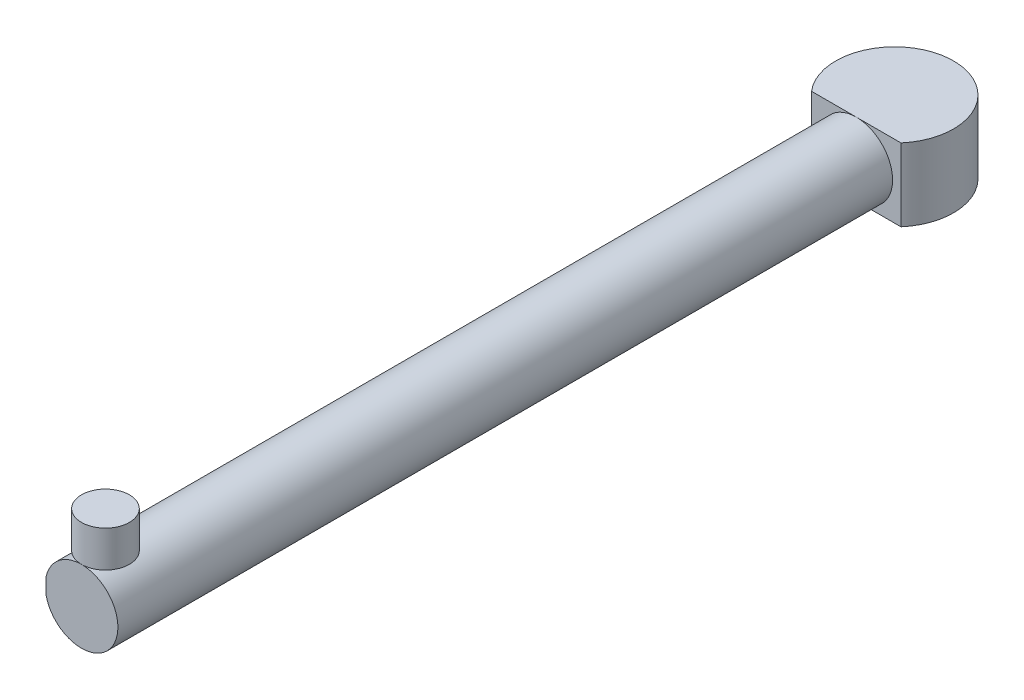
SolidWorks part; units mm, degrees
ref_plane "Front Plane" through (0, 0, 0) normal (0, 0, 1) x (1, 0, 0)
ref_plane "Top Plane" through (0, 0, 0) normal (0, 1, 0) x (1, 0, 0)
ref_plane "Right Plane" through (0, 0, 0) normal (1, 0, 0) x (0, 0, -1)
sketch "Sketch1" plane through (0, 0, 0) normal (0, 1, 0) x (1, 0, 0)
  line L2 (0, 0) -> (-74.4274, 0) construction
  line L3 (0, 0) -> (0, 54.8237) construction
  line L4 (-12.3032, 124.1682) -> (12.3032, 124.1682) construction
  line L5 (12.3032, -75.8318) -> (-12.3032, -75.8318)
  line L12 (-12.3032, 124.1682) -> (-12.3032, -75.8318)
  line L13 (12.3032, -75.8318) -> (12.3032, 124.1682)
  arc A0 (12.3032, 124.1682) -> (-12.3032, 124.1682) centre (0, 134.7355) ccw
  dimension "D2" = 200
extrude "Boss-Extrude1" add sketch "Sketch1" along normal blind 20 contours A0 L12 L5 L13
sketch "Sketch3" plane through (0, 0, 75.8318) normal (0, 0, 1) x (1, 0, 0)
  line L0 (12.3032, 0) -> (-12.3032, 0) construction
  line L1 (12.3032, 20) -> (12.3032, 0) construction
  line L2 (12.3032, 20) -> (-12.3032, 20) construction
  line L3 (-12.3032, 20) -> (-12.3032, 0) construction
  line L4 (12.3032, 0) -> (-12.3032, 0)
  line L5 (12.3032, 20) -> (12.3032, 0)
  line L6 (12.3032, 20) -> (-12.3032, 20)
  line L7 (-12.3032, 20) -> (-12.3032, 0)
  circle A0 centre (0, 10) radius 10
  line M1 (-12.3032, 0) -> (12.3032, 0)
  line M2 (12.3032, 0) -> (12.3032, 20)
  line M3 (12.3032, 20) -> (-12.3032, 20)
  line M4 (-12.3032, 20) -> (-12.3032, 0)
  dimension "D1" = 20
  dimension "D2" = 10
extrude "Cut-Extrude3" cut sketch "Sketch3" against normal blind 200 contours A0 L6 M4 M1 | A0 L4 M2 M3 region at (6.1516, 0.2348, 75.8318) region at (-6.1516, 0.2348, 75.8318)
sketch "Sketch5" plane through (0, 0, 0) normal (0, 1, 0) x (1, 0, 0)
  line L1 (10, -75.8318) -> (-9.7722, -75.8318)
  line L2 (10, -75.8318) -> (10, -89.0053)
  line L3 (10, -89.0053) -> (-9.7722, -89.0053)
  line L4 (-9.7722, -75.8318) -> (-9.7722, -89.0053)
extrude "Boss-Extrude2" add sketch "Sketch5" along normal blind 30
sketch "Sketch6" plane through (0, 30, 0) normal (0, 1, 0) x (1, 0, 0)
  line L0 (-9.7722, -89.0053) -> (10, -89.0053) construction
  line L1 (10, -75.8318) -> (-9.7722, -75.8318) construction
  line L2 (0, -75.8318) -> (-9.7722, -75.8318)
  line L3 (-9.7722, -75.8318) -> (-9.7722, -89.0053) construction
  line L4 (10, -75.8318) -> (-9.7722, -75.8318) construction
  line L5 (-9.7722, -75.8318) -> (-9.7722, -89.0053)
  line L6 (-9.7722, -89.0053) -> (0, -89.0053)
  line L7 (0, -89.0053) -> (10, -89.0053)
  line L8 (10, -89.0053) -> (10, -75.8318)
  line L9 (10, -75.8318) -> (0, -75.8318)
  circle A0 centre (0, -82.4185) radius 6.5867
  line M2 (10, -89.0053) -> (10, -75.8318)
  line M3 (10, -75.8318) -> (-9.7722, -75.8318)
  line M4 (-9.7722, -75.8318) -> (-9.7722, -89.0053)
  line M5 (-9.7722, -89.0053) -> (10, -89.0053)
extrude "Cut-Extrude6" cut sketch "Sketch6" against normal blind 10 contours A0 M3 M4 M5 | A0 M5 M2 M3 region at (-7.2377, 30, 82.4185) region at (7.3627, 30, 82.4185)
sketch "Sketch9" plane through (0, 0, 75.8318) normal (0, 0, -1) x (-1, 0, 0)
  line L0 (0, 20) -> (-10, 20) construction
  line L1 (-10, 20) -> (-10, 10) construction
  line L2 (9.7722, 20) -> (0, 20)
  line L3 (9.7722, 12.1222) -> (9.7722, 20)
  line L4 (9.7722, 20) -> (0, 20)
  line L5 (9.7722, 12.1222) -> (9.7722, 20)
  line L6 (-10, 0) -> (0, 0)
  line L7 (-10, 10) -> (-10, 0)
  line L8 (-10, 0) -> (0, 0)
  line L9 (-10, 10) -> (-10, 0)
  line L10 (9.7722, 0) -> (9.7722, 7.8778) construction
  line L11 (0, 0) -> (9.7722, 0) construction
  line L12 (0, 20) -> (-10, 20)
  line L13 (-10, 20) -> (-10, 10)
  line L14 (9.7722, 0) -> (9.7722, 7.8778)
  line L15 (0, 0) -> (9.7722, 0)
  arc A0 (0, 20) -> (-10, 10) centre (0, 10) ccw construction
  arc A1 (9.7722, 12.1222) -> (0, 20) centre (0, 10) ccw
  arc A2 (9.7722, 12.1222) -> (0, 20) centre (0, 10) ccw
  arc A3 (-10, 10) -> (0, 0) centre (0, 10) ccw
  arc A4 (-10, 10) -> (0, 0) centre (0, 10) ccw
  arc A5 (0, 0) -> (9.7722, 7.8778) centre (0, 10) ccw construction
  arc A6 (0, 20) -> (-10, 10) centre (0, 10) ccw
  arc A7 (0, 0) -> (9.7722, 7.8778) centre (0, 10) ccw
  line M7 (0, 20) -> (-10, 20)
  line M8 (-10, 20) -> (-10, 10)
  arc M9 (-10, 10) -> (0, 20) centre (0, 10) cw
  dimension "D1" = 0
  dimension "D2" = 0
extrude "Cut-Extrude8" cut sketch "Sketch9" against normal blind 34 contours A2 L5 L4 | A7 L15 L14 | M9 M7 M8 | A4 L8 L9 region at (-7.5535, 17.974, 75.8318) region at (-7.5535, 2.026, 75.8318) region at (7.7663, 17.7663, 75.8318)
